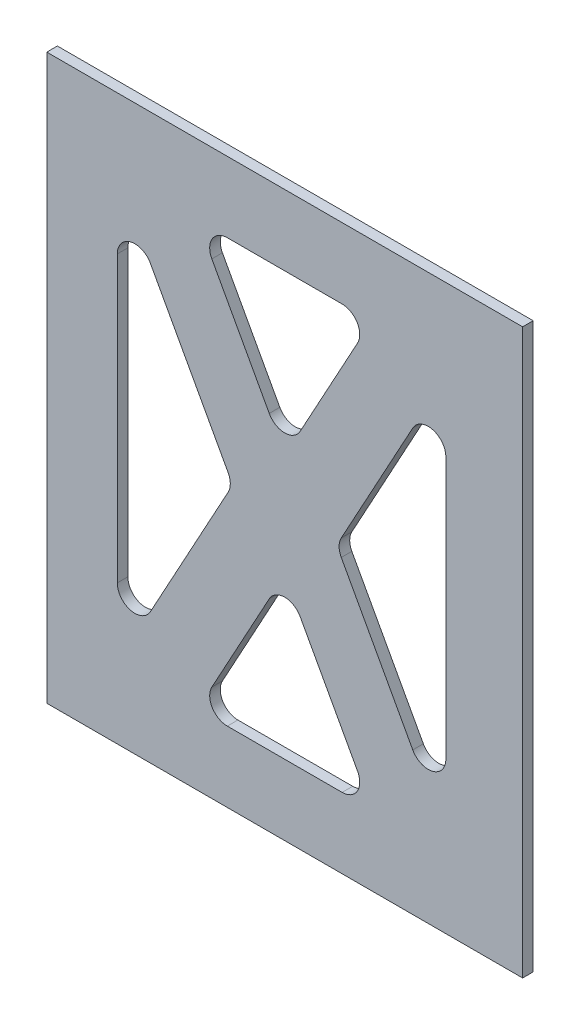
SolidWorks part; units mm, degrees
ref_plane "Front Plane" through (0, 0, 0) normal (0, 0, 1) x (1, 0, 0)
ref_plane "Top Plane" through (0, 0, 0) normal (0, 1, 0) x (1, 0, 0)
ref_plane "Right Plane" through (0, 0, 0) normal (1, 0, 0) x (0, 0, -1)
sketch "Sketch1" plane through (0, 0, 152) normal (0, 0, 1) x (1, 0, 0)
  line L1 (-67.5, 80) -> (67.5, 80)
  line L2 (-67.5, 80) -> (-67.5, -80)
  line L3 (-67.5, -80) -> (67.5, -80)
  line L4 (67.5, 80) -> (67.5, -80)
  line L6 (-47.5, -40.4093) -> (-47.5, 40.4093)
  line L7 (-38.1116, 42.8054) -> (-16.0476, 2.3961)
  line L8 (234.5, 75) -> (-65.5, 75) construction
  line L9 (-65.5, -75) -> (-65.5, 75) construction
  line L10 (234.5, -75) -> (-65.5, -75) construction
  line L12 (65.5, -75) -> (-65.5, -75) construction
  line L13 (65.5, 75) -> (65.5, -75) construction
  line L14 (-65.5, -75) -> (-65.5, 75) construction
  line L15 (-65.5, 75) -> (65.5, 75) construction
  line L18 (16.2861, 60) -> (-16.2861, 60)
  line L19 (-16.0476, -2.3961) -> (-38.1116, -42.8054)
  line L20 (-20.6745, 52.6039) -> (-4.3884, 22.7765)
  line L21 (4.3884, 22.7765) -> (20.6745, 52.6039)
  line L23 (36.3286, 39.5399) -> (16.0476, 2.3961)
  line L24 (45.717, -37.1438) -> (45.717, 37.1438)
  line L25 (16.0476, -2.3961) -> (36.3286, -39.5399)
  line L26 (-65.5, 0) -> (65.5, 0) construction
  line L27 (-20.6745, -52.6039) -> (-4.3884, -22.7765)
  line L28 (16.2861, -60) -> (-16.2861, -60)
  line L29 (4.3884, -22.7765) -> (20.6745, -52.6039)
  line L30 (0, 14.7393) -> (0, -14.7393) construction
  line L31 (-14.7393, 0) -> (14.7393, 0) construction
  line L32 (0, 14.7393) -> (0, -14.7393) construction
  arc A0 (-38.1116, -42.8054) -> (-47.5, -40.4093) centre (-42.5, -40.4093) cw
  arc A1 (-16.0476, -2.3961) -> (-16.0476, 2.3961) centre (-20.436, 0) ccw
  arc A2 (-38.1116, 42.8054) -> (-47.5, 40.4093) centre (-42.5, 40.4093) ccw
  arc A3 (20.6745, -52.6039) -> (16.2861, -60) centre (16.2861, -55) cw
  arc A4 (-20.6745, -52.6039) -> (-16.2861, -60) centre (-16.2861, -55) ccw
  arc A5 (-4.3884, -22.7765) -> (4.3884, -22.7765) centre (0, -25.1727) cw
  arc A6 (16.0476, 2.3961) -> (16.0476, -2.3961) centre (20.436, 0) ccw
  arc A7 (36.3286, -39.5399) -> (45.717, -37.1438) centre (40.717, -37.1438) ccw
  arc A8 (45.717, 37.1438) -> (36.3286, 39.5399) centre (40.717, 37.1438) ccw
  arc A9 (-20.6745, 52.6039) -> (-16.2861, 60) centre (-16.2861, 55) cw
  arc A10 (20.6745, 52.6039) -> (16.2861, 60) centre (16.2861, 55) ccw
  arc A11 (4.3884, 22.7765) -> (-4.3884, 22.7765) centre (0, 25.1727) cw
  point P14 (0, 0)
  point P15 (0, 0)
  point P32 (-47.5, 60)
  point P35 (24.7129, -60)
  point P38 (-24.7129, -60)
  point P51 (-24.7129, 60)
  point P54 (24.7129, 60)
  dimension "D9" = 5
  dimension "D10" = 5
  dimension "D1" = 2
  dimension "D2" = 2
  dimension "D3" = 5
  dimension "D4" = 5
  dimension "D5" = 20
  dimension "D6" = 20
  dimension "D7" = 20
  dimension "D8" = 20
extrude "Boss-Extrude1" add sketch "Sketch1" along normal blind 3
